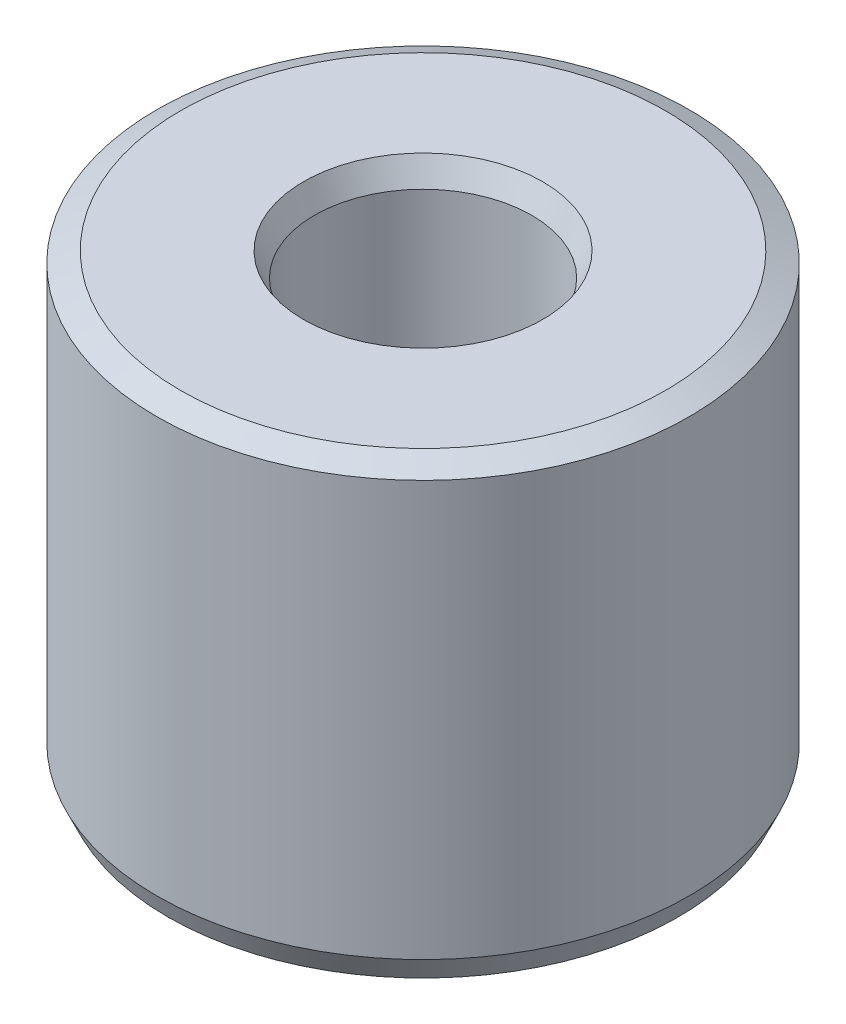
SolidWorks part; units mm, degrees
ref_plane "Front Plane" through (0, 0, 0) normal (0, 0, 1) x (1, 0, 0)
ref_plane "Top Plane" through (0, 0, 0) normal (0, 1, 0) x (1, 0, 0)
ref_plane "Right Plane" through (0, 0, 0) normal (1, 0, 0) x (0, 0, -1)
sketch "Sketch1" plane through (0, 0, 0) normal (0, 1, 0) x (1, 0, 0)
  circle A0 centre (0, 0) radius 27.5
  dimension "SLEEVE_OD" = 55
extrude "Boss-Extrude1" add sketch "Sketch1" along normal blind 46.4651
sketch "Sketch2" plane through (0, 0, 0) normal (0, 1, 0) x (1, 0, 0)
  circle A0 centre (0, 0) radius 11.2279
  dimension "BORE_D" = 22.4558
extrude "Cut-Extrude1" cut sketch "Sketch2" along normal through all
chamfer "Chamfer1" distance 1.1259 angle 65.297 4 edges at (0, 46.4651, 11.2279) (0, 0, 11.2279) (0, 0, 27.5) (0, 46.4651, 27.5) first distance on face at (0, 46.4651, 11.2279) first distance on face at (0, 0, 11.2279) first distance on face at (0, 46.4651, 27.5)
